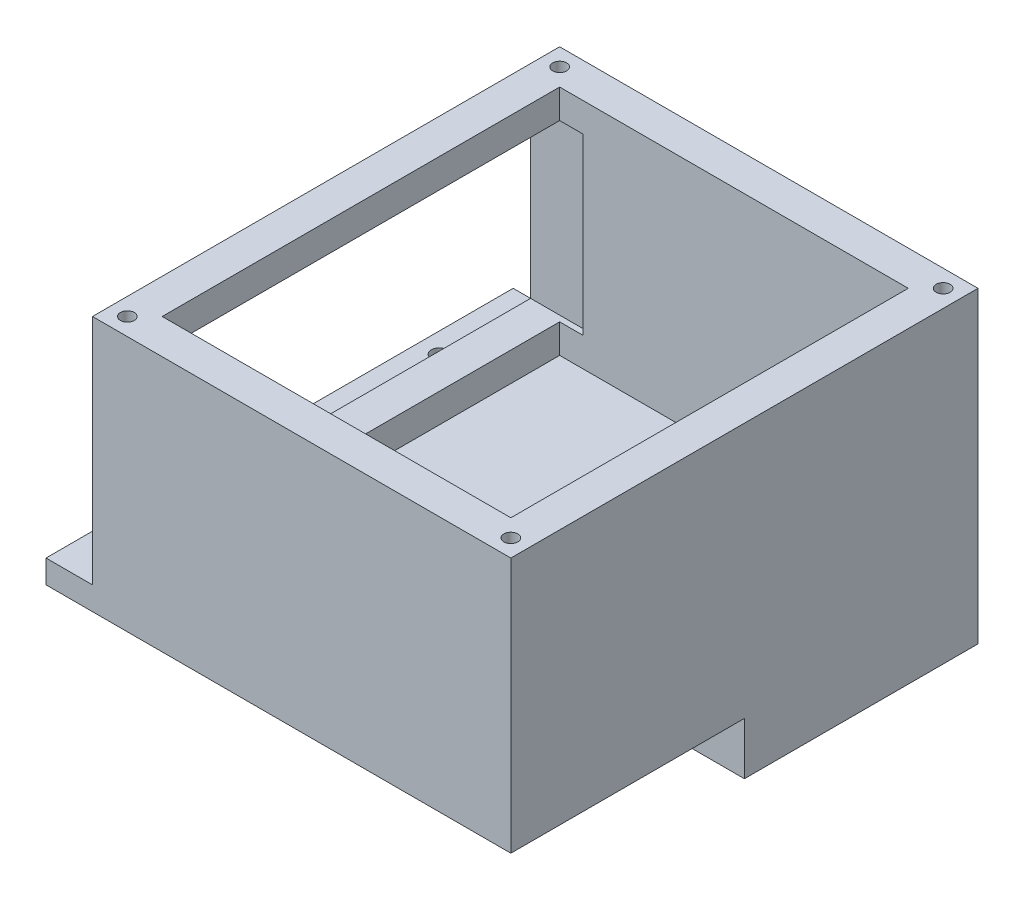
SolidWorks part; units mm, degrees
ref_plane "Front Plane" through (0, 0, 0) normal (0, 0, 1) x (1, 0, 0)
ref_plane "Top Plane" through (0, 0, 0) normal (0, 1, 0) x (1, 0, 0)
ref_plane "Right Plane" through (0, 0, 0) normal (1, 0, 0) x (0, 0, -1)
sketch "Sketch1" plane through (0, 0, 0) normal (0, 1, 0) x (1, 0, 0)
  line L1 (-40, -40.2) -> (40, -40.2)
  line L2 (-40, -40.2) -> (-40, 40.2)
  line L3 (-40, 40.2) -> (40, 40.2)
  line L4 (40, -40.2) -> (40, 40.2)
  line L5 (-40, -40.2) -> (40, 40.2) construction
  line L6 (-40, 40.2) -> (40, -40.2) construction
  point P0 (0, 0)
  dimension "D1" = 80.4
  dimension "D2" = 80
extrude "Boss-Extrude1" add sketch "Sketch1" along normal blind 4
sketch "Sketch3" plane through (0, 0, 0) normal (0, -1, 0) x (1, 0, 0)
  line L8 (40, 0) -> (-30, 0)
  line L10 (40, -40.2) -> (-30, -40.2)
  line L11 (40, -40.2) -> (40, 0)
  line L12 (40, 0) -> (-30, 0)
  line L13 (-30, -40.2) -> (-30, 0)
  line M2 (40, -40.2) -> (40, 40.2)
  line M5 (-40, -40.2) -> (40, -40.2)
  dimension "D1" = 70
  dimension "D2" = 40.2
extrude "Boss-Extrude3" add sketch "Sketch3" along normal blind 9 contours L13 L8 M5 M2 region at (5, 0, -20.1)
sketch "Sketch4" plane through (0, -9, 0) normal (0, -1, 0) x (1, 0, 0)
  line L2 (7.15, 0) -> (-7.15, 0) construction
  line L4 (-40, -40.2) -> (-40, 40.2) construction
  line L5 (40, 0) -> (-30, 0) construction
  circle A0 centre (-36.5, 24) radius 1.375
  circle A1 centre (-36.5, -24) radius 1.375
  dimension "D1" = 2.75
  dimension "D2" = 24
  dimension "D3" = 3.5
extrude "Cut-Extrude1" cut sketch "Sketch4" against normal blind 19
sketch "Sketch6" plane through (0, 4, 0) normal (0, 1, 0) x (1, 0, 0)
  line L1 (-40, 40.2) -> (-40, -40.2) construction
  line L2 (-27, -35.2) -> (35, -35.2)
  line L3 (-27, -35.2) -> (-27, 0)
  line L4 (35, -35.2) -> (35, 35.2)
  line L5 (35, -35.2) -> (35, 35.2)
  line L9 (35, 35.2) -> (-35, 35.2)
  line L10 (-35, 35.2) -> (-35, -35.2)
  line L11 (-35, -35.2) -> (35, -35.2)
  line L19 (35, 35.2) -> (-27, 35.2)
  line L20 (35, 35.2) -> (35, -35.2)
  line L21 (35, -35.2) -> (-27, -35.2)
  line L22 (-27, 35.2) -> (-27, -35.2)
  line L23 (-27, 0) -> (35, 0)
  line L24 (35, -35.2) -> (35, 0)
  dimension "D2" = 13
  dimension "D1" = 5
extrude "Cut-Extrude4" cut sketch "Sketch6" against normal up to next contours L3 L2 L24 L23
sketch "Sketch7" plane through (0, 4, 0) normal (0, -1, 0) x (1, 0, 0)
  line L9 (-30, -40.2) -> (-40, -40.2) construction
  line L10 (40, 40.2) -> (-32, 40.2)
  line L11 (40, 40.2) -> (40, -40.2)
  line L12 (40, -40.2) -> (-32, -40.2)
  line L13 (-32, 40.2) -> (-32, -40.2)
  line L14 (34, 34.2) -> (34, -34.2)
  line L15 (34, -34.2) -> (-26, -34.2)
  line L16 (-26, 34.2) -> (-26, -34.2)
  line L17 (34, 34.2) -> (-26, 34.2)
  dimension "D2" = 72
  dimension "D1" = 6
extrude "Boss-Extrude4" add sketch "Sketch7" against normal blind 40
sketch "Sketch9" plane through (0, 44, 0) normal (0, 1, 0) x (1, 0, 0)
  line L16 (37, -37.2) -> (37, 37.2)
  line L17 (37, 37.2) -> (-29, 37.2)
  line L18 (-29, 37.2) -> (-29, -37.2)
  line L19 (-29, -37.2) -> (37, -37.2)
  line L20 (37, -37.2) -> (37, 37.2)
  line L21 (37, 37.2) -> (-29, 37.2)
  line L22 (-29, 37.2) -> (-29, -37.2)
  line L23 (-29, -37.2) -> (37, -37.2)
  circle A0 centre (-29, 37.2) radius 1.2
  circle A1 centre (37, 37.2) radius 1.2
  circle A2 centre (37, -37.2) radius 1.2
  circle A3 centre (-29, -37.2) radius 1.2
  dimension "D1" = 2.4
  dimension "D2" = 2.4
  dimension "D3" = 2.4
  dimension "D7" = 2.4
  dimension "D4" = 3
extrude "Cut-Extrude5" cut sketch "Sketch9" against normal blind 10 contours A0 | A3 | A2 | A1
sketch "Sketch10" plane through (-32, 0, 0) normal (-1, 0, 0) x (0, 0, 1)
  line L8 (-35.2, 9) -> (35.2, 9)
  line L9 (35.2, 9) -> (35.2, 39)
  line L10 (35.2, 39) -> (-35.2, 39)
  line L11 (-35.2, 39) -> (-35.2, 9)
  line L12 (-35.2, 9) -> (35.2, 9)
  line L13 (35.2, 9) -> (35.2, 39)
  line L14 (35.2, 39) -> (-35.2, 39)
  line L15 (-35.2, 39) -> (-35.2, 9)
  dimension "D1" = 5
extrude "Cut-Extrude6" cut sketch "Sketch10" against normal blind 10
sketch "Sketch11" plane through (0, 9, 0) normal (0, 1, 0) x (1, 0, 0)
  line L0 (-26, 34.2) -> (-26, -34.2) construction
  line L1 (-32, -35.2) -> (-26, -35.2)
  line L2 (-32, -35.2) -> (-32, 0)
  line L3 (-32, 0) -> (-26, 0)
  line L4 (-26, -35.2) -> (-26, 0)
  line L6 (-26, 0) -> (-23.9815, 0)
  line L7 (-26, 0) -> (-26, -35.2)
  line L8 (-26, -35.2) -> (-23.9815, -35.2)
  line L9 (-23.9815, 0) -> (-23.9815, -35.2)
  line M5 (-26, -34.2) -> (-26, 34.2)
  line M12 (-22, -34.2) -> (-26, -34.2)
extrude "Cut-Extrude7" cut sketch "Sketch11" against normal blind 17 contours L9 L6 M5 M12 | L2 L1 L4 L3 | L7 L6 L9 L8 region at (-24.9907, 9, 17.1)
fillet "Fillet1" radius 2.4 2 edges at (-30, 0, -20.1) (-32, 4, -20.1)
